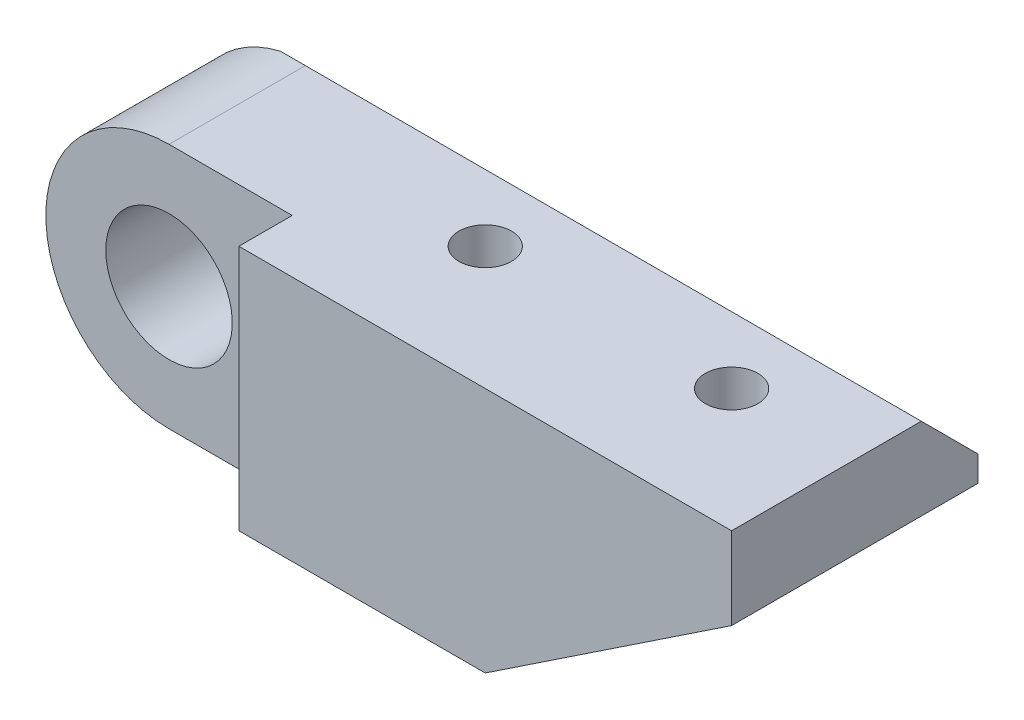
SolidWorks part; units mm, degrees
ref_plane "Front Plane" through (0, 0, 0) normal (0, 0, 1) x (1, 0, 0)
ref_plane "Top Plane" through (0, 0, 0) normal (0, 1, 0) x (1, 0, 0)
ref_plane "Right Plane" through (0, 0, 0) normal (1, 0, 0) x (0, 0, -1)
sketch "Sketch1" plane through (0, 0, 0) normal (0, 0, 1) x (1, 0, 0)
  line L0 (0, 0) -> (-15, 0)
  line L1 (0, 0) -> (60, 0)
  line L2 (0, 0) -> (0, -30)
  line L3 (0, -30) -> (60, -30)
  line L4 (60, 0) -> (60, -30)
  line L5 (-30, -15) -> (-30, 3.2539)
  line L6 (0, -30) -> (-15, -30)
  line L7 (0, 0) -> (0, -30)
  line L8 (-15, -30) -> (0, -30)
  line L9 (-15, 0) -> (0, 0)
  arc A0 (-15, -30) -> (-15, 0) centre (-15, -15) cw
  dimension "D1" = 60
  dimension "D2" = 30
  dimension "D3" = 30
extrude "Boss-Extrude2" add sketch "Sketch1" along normal blind 30 contours L2 L1 L4 L3
sketch "Sketch2" plane through (0, 0, 30) normal (0, 0, 1) x (1, 0, 0)
  line L0 (0, -30) -> (-15, -30) construction
  line L1 (0, 0) -> (-15, 0) construction
  line L2 (0, -30) -> (-15, -30)
  line L3 (0, 0) -> (-15, 0)
  arc A0 (-15, 0) -> (-15, -30) centre (-15, -15) ccw construction
  arc A1 (-15, 0) -> (-15, -30) centre (-15, -15) ccw
sketch "Sketch3" plane through (0, 0, 30) normal (0, 0, 1) x (1, 0, 0)
  line L0 (0, 0) -> (-15, 0)
  line L1 (0, -30) -> (-15, -30)
  line L2 (0, 0) -> (0, -30)
  arc A0 (-15, -30) -> (-15, 0) centre (-15, -15) cw
extrude "Boss-Extrude3" add sketch "Sketch3" against normal blind 30
sketch "Sketch4" plane through (0, 0, 30) normal (0, 0, 1) x (1, 0, 0)
  line L6 (-15, -30) -> (60, -30)
  line L7 (60, -30) -> (60, 0)
  line L8 (60, 0) -> (-15, 0)
  line L9 (-15, -30) -> (60, -30)
  line L10 (60, -30) -> (60, 0)
  line L11 (60, 0) -> (-15, 0)
  arc A2 (-15, 0) -> (-15, -30) centre (-15, -15) ccw
  arc A3 (-15, 0) -> (-15, -30) centre (-15, -15) ccw
  dimension "D1" = 0
sketch "Sketch5" plane through (0, 0, 30) normal (0, 0, 1) x (1, 0, 0)
  line L0 (0, 0) -> (0, -30)
  line L1 (0, -30) -> (-15, -30)
  line L2 (0, 0) -> (-15, 0)
  arc A0 (-15, -30) -> (-15, 0) centre (-15, -15) cw
extrude "Cut-Extrude1" cut sketch "Sketch5" against normal blind 6.5
sketch "Sketch6" plane through (0, 0, 0) normal (0, 0, -1) x (-1, 0, 0)
  line L0 (0, 0) -> (0, -30)
  line L1 (0, -30) -> (15, -30)
  line L2 (0, 0) -> (15, 0)
  arc A0 (15, 0) -> (15, -30) centre (15, -15) cw
extrude "Cut-Extrude2" cut sketch "Sketch6" against normal blind 6.5
sketch "Sketch7" plane through (0, 0, 6.5) normal (0, 0, -1) x (-1, 0, 0)
  circle A0 centre (15, -15) radius 7.7
  dimension "D1" = 15.4
extrude "Cut-Extrude3" cut sketch "Sketch7" against normal through all both and the other way through all
sketch "Sketch8" plane through (0, -30, 0) normal (0, -1, 0) x (1, 0, 0)
  line L0 (0, 30) -> (0, 0) construction
  line L1 (0, 0) -> (0, 15) construction
  line L2 (0, 15) -> (60, 15) construction
  line L3 (60, 30) -> (60, 0) construction
  line L4 (15, 30) -> (15, 0)
  line L5 (60, 30) -> (-15, 30) construction
  line L6 (0, 0) -> (60, 0) construction
  line L7 (45, 30) -> (45, 0)
  circle A0 centre (15, 15) radius 6
  circle A1 centre (45, 15) radius 6
  dimension "D3" = 12
  dimension "D4" = 12
  dimension "D1" = 15
  dimension "D2" = 15
extrude "Cut-Extrude6" cut sketch "Sketch8" against normal blind 6 contours A0
sketch "Sketch9" plane through (0, -30, 0) normal (0, -1, 0) x (1, 0, 0)
  circle A0 centre (45, 15) radius 6 construction
  circle A1 centre (45, 15) radius 6
extrude "Cut-Extrude7" cut sketch "Sketch9" against normal blind 16
sketch "Sketch10" plane through (0, -24, 0) normal (0, -1, 0) x (1, 0, 0)
  circle A0 centre (15, 15) radius 3.2
  circle A1 centre (45, 15) radius 3.2
  dimension "D1" = 6.4
  dimension "D2" = 6.4
extrude "Cut-Extrude8" cut sketch "Sketch10" against normal through all
chamfer "Chamfer2" distance 30 distance2 20 1 edges at (60, -30, 15) first distance on face at (45, -30, 9)
sketch "Sketch11" plane through (0, 0, 0) normal (-1, 0, 0) x (0, 0, 1)
  line L0 (6.5, 0) -> (23.5, 0) construction
  line L1 (6.5, 0) -> (23.5, 0)
  line L2 (6.9, 0) -> (0, -6.9)
  line L4 (0, 0) -> (0, -30)
  line L5 (0, -30) -> (6.5, -30)
  line L6 (6.5, -30) -> (6.5, 0)
  line L7 (6.5, 0) -> (0, 0)
  line L8 (0, 0) -> (0, -30)
  line L9 (0, -30) -> (6.5, -30)
  line L10 (6.5, -30) -> (6.5, 0)
  line L11 (6.5, 0) -> (0, 0)
  line M5 (0, 0) -> (0, -30)
  line M7 (6.5, -30) -> (6.5, 0)
  line M8 (6.5, 0) -> (0, 0)
  dimension "D2" = 45
  dimension "D3" = 0.4
  dimension "D1" = 0
extrude "Cut-Extrude9" cut sketch "Sketch11" against normal through all both and the other way through all contours L2 M7 M8 M5 | L2 L1 M7 region at (0, -0.1333, 6.6333) region at (0, -2.3073, 2.2854)
